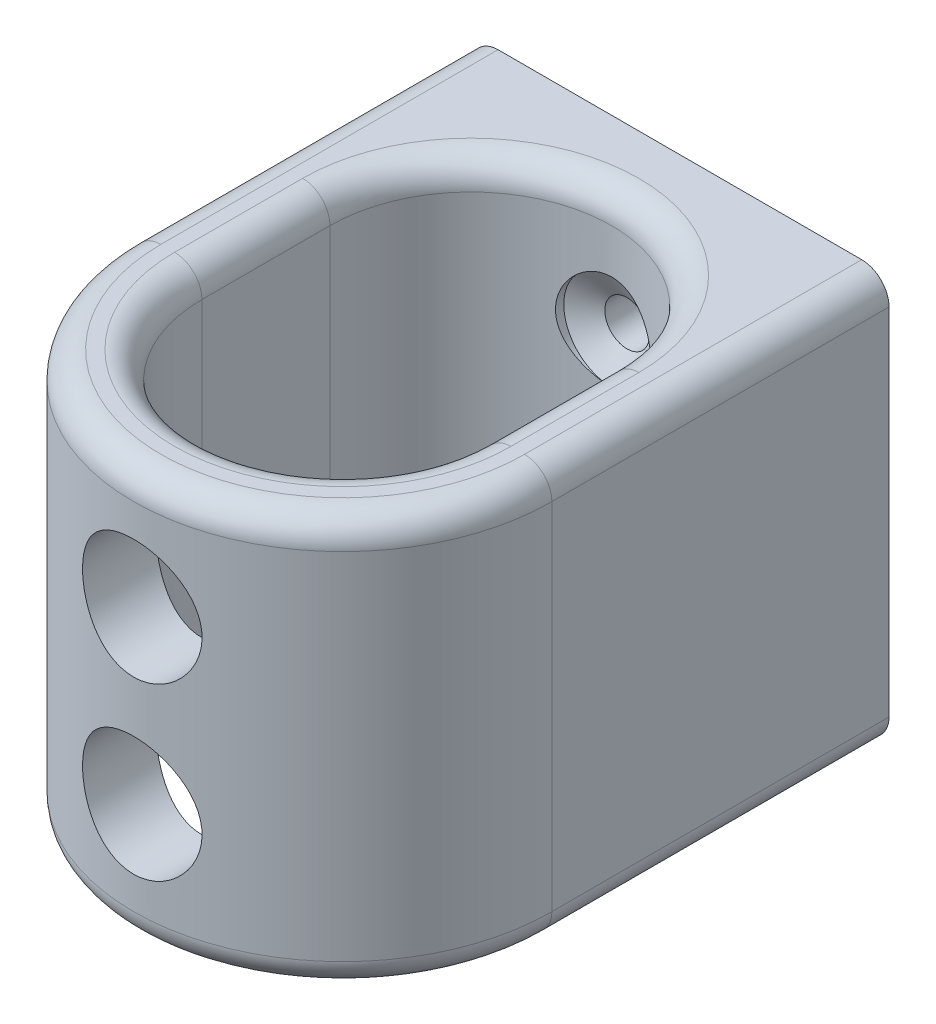
SolidWorks part; units mm, degrees
ref_plane "Front Plane" through (0, 0, 0) normal (0, 0, 1) x (1, 0, 0)
ref_plane "Top Plane" through (0, 0, 0) normal (0, 1, 0) x (1, 0, 0)
ref_plane "Right Plane" through (0, 0, 0) normal (1, 0, 0) x (0, 0, -1)
sketch "Sketch1" plane through (0, 0, 0) normal (0, 1, 0) x (1, 0, 0)
  line L0 (0, 0) -> (0, 11.9063) construction
  line L1 (-13.0969, 0) -> (-13.0969, 11.9063)
  line L2 (13.0969, 0) -> (13.0969, 11.9063)
  line L3 (0, 0) -> (0, 11.9063) construction
  line L4 (-19.4469, 0) -> (-19.4469, 11.9063)
  line L5 (19.4469, 0) -> (19.4469, 11.9063)
  line L6 (-19.4469, 11.9063) -> (-19.4469, 31.3531)
  line L7 (-19.4469, 31.3531) -> (19.4469, 31.3531)
  line L8 (19.4469, 31.3531) -> (19.4469, 11.9063)
  arc A0 (-13.0969, 0) -> (13.0969, 0) centre (0, 0) ccw
  arc A1 (13.0969, 11.9063) -> (-13.0969, 11.9063) centre (0, 11.9063) ccw
  arc A2 (-19.4469, 0) -> (19.4469, 0) centre (0, 0) ccw
  arc A3 (19.4469, 11.9063) -> (-19.4469, 11.9063) centre (0, 11.9063) ccw
  point P3 (0, 5.9531)
  point P8 (0, 25.0031)
  point P9 (0, -13.0969)
  point P12 (0, 5.9531)
  point P23 (0, 31.3531)
  dimension "D1" = 38.1
  dimension "D2" = 26.1937
  dimension "D3" = 6.35
extrude "Boss-Extrude1" add sketch "Sketch1" along normal mid plane 38.1 contours A3 L7 L6 | L5 A3 L4 A2 A1 L2 A0 L1 | A3 L8 L7 region at (-18.8071, 0, -5.9531) region at (-15.1031, 0, -27.0093) region at (15.1031, 0, -27.0093)
ref_plane "Plane1" through (0, 7.9375, 0) normal (0, 1, 0) x (1, 0, 0)
ref_axis "Axis1" through (0, 7.9375, -30.5594) along (0, 0, 1)
sketch "Sketch2" plane through (0, 7.9375, 0) normal (0, 1, 0) x (1, 0, 0)
  line L0 (-2.0637, 31.3531) -> (-2.0638, 26.4339)
  line L1 (-19.4469, 31.3531) -> (19.4469, 31.3531) construction
  line L2 (-2.0638, 26.4339) -> (-4.445, 25.0031)
  line L3 (-4.445, 25.0031) -> (-4.445, 0)
  line L4 (-4.445, -19.4469) -> (0, -19.4469)
  line L5 (0, 30.5594) -> (0, -21.8281) construction
  line L6 (-2.0637, 31.3531) -> (0, 31.3531)
  line L7 (0, 28.1791) -> (0, -19.4469) construction
  line L8 (0, -19.4469) -> (0, 31.3531)
  line L9 (-4.445, 0) -> (-5.5563, 0)
  line L10 (-5.5563, 0) -> (-5.5563, -19.4469)
  line L11 (-5.5563, -19.4469) -> (-4.445, -19.4469)
  line L12 (-4.445, 0) -> (-4.445, -19.4469) construction
  arc A0 (-19.4469, 0) -> (19.4469, 0) centre (0, 0) ccw construction
  arc A1 (13.0969, 11.9063) -> (-13.0969, 11.9063) centre (0, 11.9063) ccw construction
  point P16 (0, 25.0031)
  dimension "D1" = 59
  dimension "D2" = 2.0638
  dimension "D3" = 4.445
  dimension "D4" = 5.5562
revolve "Cut-Revolve1" cut sketch "Sketch2" angle 360 about L7
mirror "Mirror1" about plane through (0, 0, 0) normal (0, 1, 0) of "Cut-Revolve1"
sketch "Sketch3" plane through (0, 19.05, 0) normal (0, 1, 0) x (1, 0, 0)
  line L0 (1.5875, -13.0969) -> (-1.5875, -13.0969) construction
  line L1 (1.5875, -16.2719) -> (-1.5875, -16.2719)
  line L2 (1.5875, -9.9219) -> (-1.5875, -9.9219)
  line L3 (0, 30.5594) -> (0, -21.8281) construction
  arc A1 (-5.5563, -11.8599) -> (5.5563, -11.8599) centre (0, 0) ccw construction
  arc A2 (1.5875, -16.2719) -> (1.5875, -9.9219) centre (1.5875, -13.0969) ccw
  arc A3 (-1.5875, -9.9219) -> (-1.5875, -16.2719) centre (-1.5875, -13.0969) ccw
  point P2 (0, -13.0969)
  point P12 (4.7625, -13.0969)
  point P13 (-4.7625, -13.0969)
  dimension "D1" = 6.35
  dimension "D2" = 9.525
extrude "Cut-Extrude1" [suppressed] cut sketch "Sketch3" against normal blind 9.525
fillet "Fillet1" radius 2.54 14 edges at (19.4469, -19.05, -15.6766) (0, -19.05, 19.4469) (13.0969, -19.05, -5.9531) (0, -19.05, 13.0969) (-13.0969, -19.05, -5.9531) (13.0969, 19.05, -5.9531) (0, 19.05, 13.0969) (-13.0969, 19.05, -5.9531) (19.4469, 19.05, -15.6766) (0, 19.05, 19.4469) (-19.4469, -19.05, -15.6766) (0, -19.05, -25.0031) (0, 19.05, -25.0031) (-19.4469, 19.05, -15.6766)
